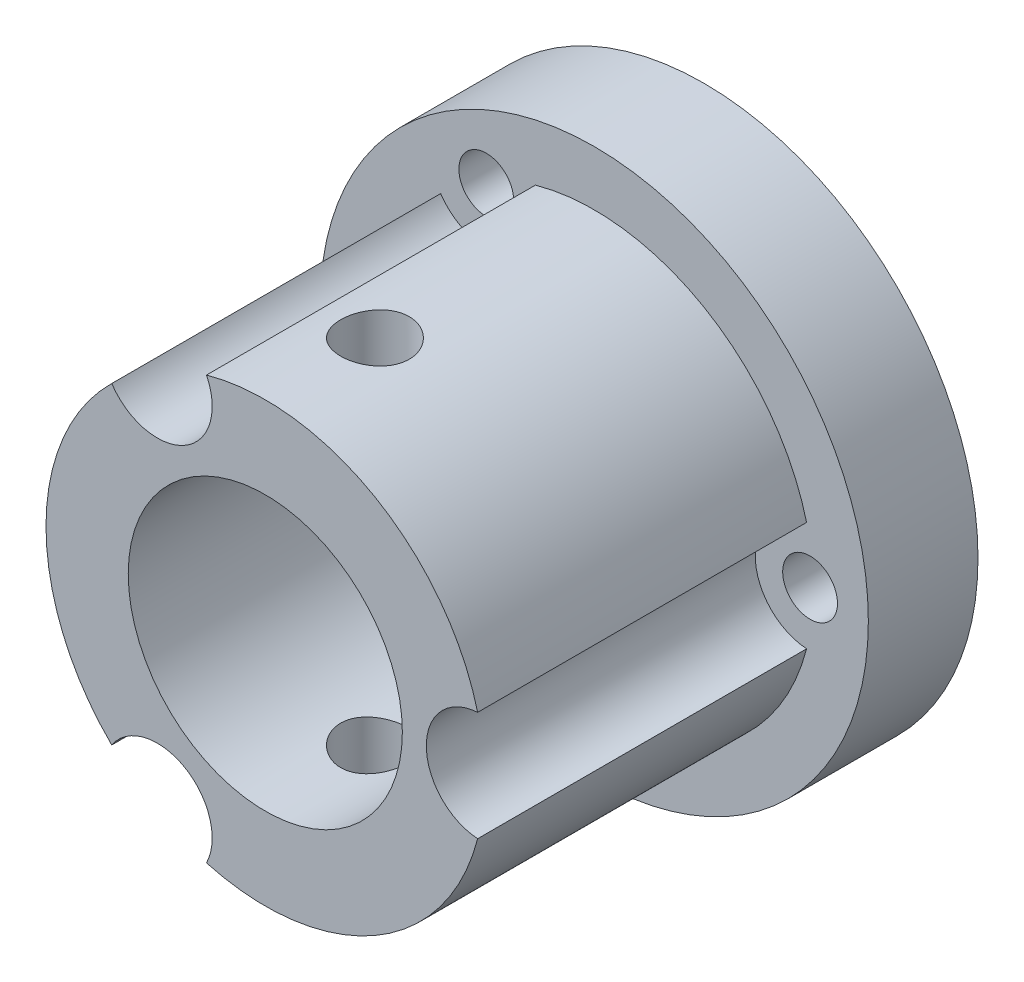
SolidWorks part; units mm, degrees
ref_plane "Front Plane" through (0, 0, 0) normal (0, 0, 1) x (1, 0, 0)
ref_plane "Top Plane" through (0, 0, 0) normal (0, 1, 0) x (1, 0, 0)
ref_plane "Right Plane" through (0, 0, 0) normal (1, 0, 0) x (0, 0, -1)
sketch "Sketch1" plane through (0, 0, 0) normal (0, 0, 1) x (1, 0, 0)
  circle A0 centre (0, 0) radius 15.875
  circle A1 centre (0, 0) radius 7.9375
  dimension "D1" = 31.75
  dimension "D2" = 15.875
extrude "Boss-Extrude1" add sketch "Sketch1" along normal blind 6.35
sketch "Sketch2" plane through (0, 0, 6.35) normal (0, 0, 1) x (1, 0, 0)
  circle A0 centre (0, 0) radius 14.29
  circle M2 centre (0, 0) radius 7.9375
  dimension "D1" = 28.58
extrude "Boss-Extrude2" add sketch "Sketch2" along normal blind 19.05 contours A0 M2 region at (-13.8858, 0, 6.35)
sketch "Sketch3" plane through (0, 0, 0) normal (0, 0, -1) x (-1, 0, 0)
  line L1 (0, 0) -> (11.5089, -19.934) construction
  line L2 (0, 0) -> (-25, 0) construction
  line L3 (6.25, 10.8253) -> (0, 0) construction
  line L4 (3.4925, 0) -> (-3.4925, 0) construction
  circle A0 centre (0, 0) radius 12.5 construction
  circle A1 centre (6.25, 10.8253) radius 1.5875
  circle A2 centre (6.25, -10.8253) radius 1.5875
  circle A3 centre (-12.5, 0) radius 1.5875
  dimension "D3" = 25
  dimension "D4" = 3.175
  dimension "D5" = 3.175
  dimension "D6" = 3.175
  dimension "D7" = 120
  dimension "D1" = 120
  dimension "D2" = 60
extrude "Cut-Extrude1" cut sketch "Sketch3" against normal blind 14.8
ref_axis "Axis1" through (0, 0, 25.4) along (0, 0, -1)
sketch "Sketch4" plane through (0, 0, 0) normal (0, 1, 0) x (1, 0, 0)
  line L0 (0, -11.7425) -> (0, 11.7425) construction
  line L1 (-14.29, -25.4) -> (14.29, -25.4) construction
  circle A0 centre (0, -19.05) radius 1.9844
  dimension "D1" = 3.9688
  dimension "D2" = 6.35
extrude "Cut-Extrude3" cut sketch "Sketch4" against normal through all and the other way through all
ref_axis "Axis2" through (12.5, 0, 14.8) along (0, 0, -1)
sketch "Sketch5" plane through (0, 0, 25.4) normal (0, 0, 1) x (1, 0, 0)
  circle A0 centre (-6.25, 10.8253) radius 3.175
  circle A1 centre (12.5, 0) radius 3.175
  circle A2 centre (-6.25, -10.8253) radius 3.175
  dimension "D1" = 6.35
  dimension "D2" = 6.35
  dimension "D3" = 6.35
extrude "Cut-Extrude4" cut sketch "Sketch5" against normal up to surface (19.05 mm away) up to face at (14.29, 0, 6.35)
sketch "Sketch6" plane through (0, 0, 25.4) normal (0, 0, 1) x (1, 0, 0)
  circle A0 centre (0, 0) radius 12.7
  circle A2 centre (0, 0) radius 15.875
  circle A3 centre (0, 0) radius 15.875
  arc M1 (-9.4239, -10.7422) -> (-4.591, -13.5324) centre (-6.25, -10.8253) cw
  arc M2 (-4.591, -13.5324) -> (14.0149, -2.7903) centre (0, 0) ccw
  arc M3 (14.0149, -2.7903) -> (14.0149, 2.7903) centre (12.5, 0) cw
  arc M4 (14.0149, 2.7903) -> (-4.591, 13.5324) centre (0, 0) ccw
  arc M5 (-4.591, 13.5324) -> (-9.4239, 10.7422) centre (-6.25, 10.8253) cw
  arc M6 (-9.4239, 10.7422) -> (-9.4239, -10.7422) centre (0, 0) ccw
  dimension "D1" = 25.4
  dimension "D2" = 0
extrude "Cut- Change from .065 WT to .125" cut sketch "Sketch6" against normal up to surface (19.05 mm away) contours A3 A0 M5 M4 M3 M2 M1 M6 | A0 M1 M2 M3 | A0 M5 M6 M1 | A0 M3 M4 M5 region at (6.4594, 11.1879, 25.4) region at (13.2304, -3.3142, 25.4) region at (-12.9215, 0, 25.4) region at (-15.426, 0, 25.4) up to face at (0, 0, 6.35)
equation "\"D3@Sketch5\"=\"D1@Sketch5\""
equation "\"D2@Sketch5\"=\"D1@Sketch5\""
equation "\"D6@Sketch3\"=\"D5@Sketch3\""
equation "\"D4@Sketch3\"=\"D5@Sketch3\""
